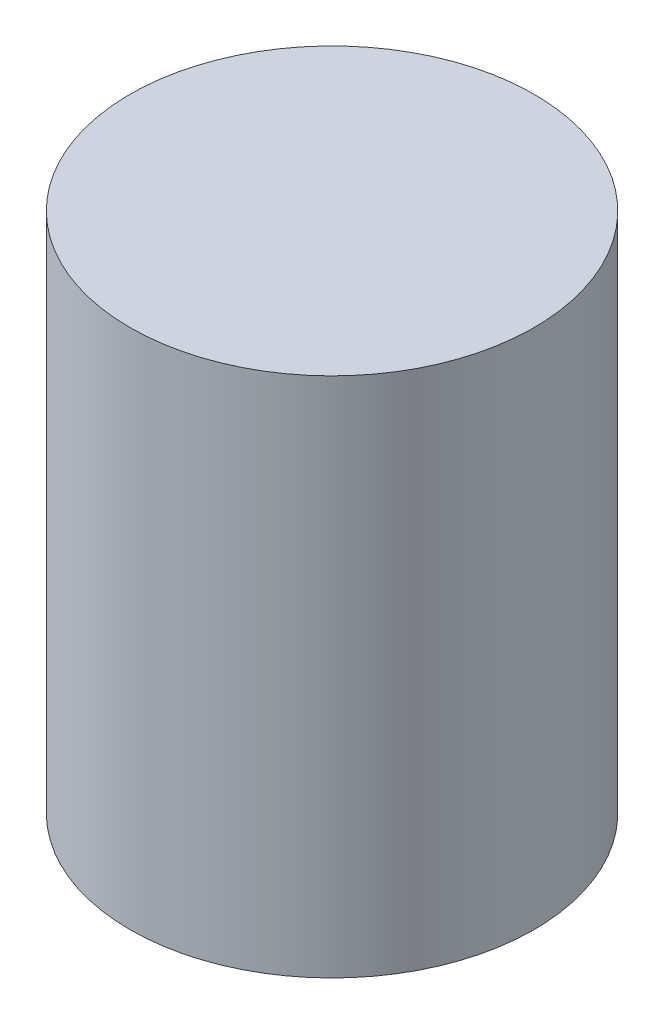
SolidWorks part; units mm, degrees
ref_plane "Front Plane" through (0, 0, 0) normal (0, 0, 1) x (1, 0, 0)
ref_plane "Top Plane" through (0, 0, 0) normal (0, 1, 0) x (1, 0, 0)
ref_plane "Right Plane" through (0, 0, 0) normal (1, 0, 0) x (0, 0, -1)
sketch "Sketch1" plane through (0, 0, 0) normal (0, 1, 0) x (1, 0, 0)
  circle A0 centre (0, 0) radius 3.1
  circle A1 centre (0, 0) radius 1.975
  dimension "D1" = 6.2
  dimension "D2" = 3.95
extrude "Boss-Extrude1" add sketch "Sketch1" along normal blind 8 contours A1 | A0 A1 region at (-3.0123, 0, 0) region at (0, 0, 0)
extrude "Cut-Extrude1" cut sketch "Sketch1<4>" along normal offset from surface (6 mm away) 2 contours A1 region at (0, 0, 0) up to face at (0, 8, 3.1)
sketch "Sketch1<4>" plane through (0, 0, 0) normal (0, 1, 0) x (1, 0, 0) same geometry as "Sketch1"
